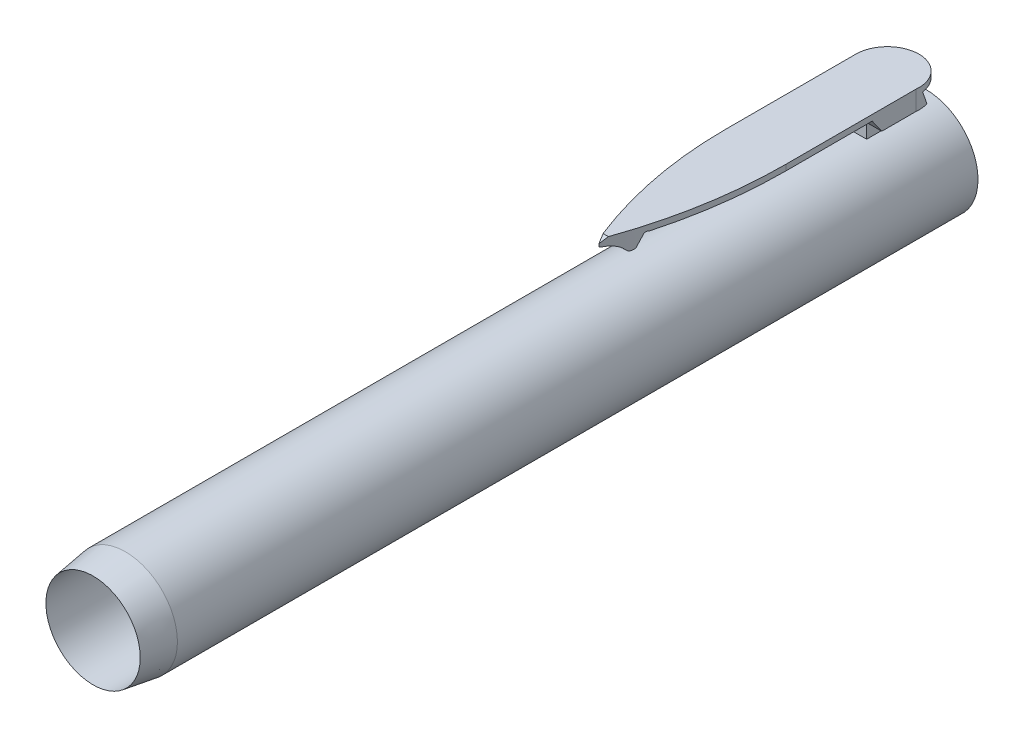
SolidWorks part; units mm, degrees
material "Cast Alloy Steel"
ref_plane "Front Plane" through (0, 0, 0) normal (0, 0, 1) x (1, 0, 0)
ref_plane "Top Plane" through (0, 0, 0) normal (0, 1, 0) x (1, 0, 0)
ref_plane "Right Plane" through (0, 0, 0) normal (1, 0, 0) x (0, 0, -1)
ref_axis "X-axis" through (-88.99, 0, 0) along (1, 0, 0)
ref_axis "Y-axis" through (0, 55, 0) along (0, -1, 0)
ref_axis "Z-axis" through (0, 0, -88.99) along (0, 0, 1)
sketch "Sketch2" plane through (0, 0, 0) normal (1, 0, 0) x (0, 0, -1)
  line L0 (0, 0) -> (60.3829, 0) construction
  line L1 (0, 6.1849) -> (106.7469, 6.1849)
  line L2 (0, 6.1849) -> (4.2394, 6.8199)
  line L3 (4.2394, 6.8199) -> (109.22, 6.8199)
  line L4 (109.22, 6.8199) -> (109.22, 6.1849)
  line L5 (106.7469, 6.1849) -> (106.7469, 3.81)
  line L6 (106.7469, 3.81) -> (109.22, 3.81)
  line L7 (109.22, 3.81) -> (109.22, 6.1849)
  dimension "D1" = 12.3698
  dimension "D2" = 109.22
  dimension "D3" = 0.635
  dimension "D4" = 7.62
revolve "Revolve1" add sketch "Sketch2" angle 360 about L0
ref_plane "Plane1" through (0, 6.8199, 0) normal (0, 1, 0) x (1, 0, 0)
sketch "Sketch3" plane through (0, 6.8199, 0) normal (0, 1, 0) x (1, 0, 0)
  line L1 (-1.761, 99.6768) -> (1.761, 99.6768)
  line L2 (-1.761, 99.6768) -> (-1.761, 105.7522)
  line L3 (-1.761, 105.7522) -> (1.761, 105.7522)
  line L4 (1.761, 99.6768) -> (1.761, 105.7522)
  line L5 (-1.761, 99.6768) -> (1.761, 105.7522) construction
  line L6 (-1.761, 105.7522) -> (1.761, 99.6768) construction
  point P0 (0, 102.7145)
extrude "Boss-Extrude1" add sketch "Sketch3" along normal blind 1.905 separate body
sketch "Sketch4" plane through (0, 8.7249, 0) normal (0, 1, 0) x (1, 0, 0)
  line L0 (-4.1727, 104.1606) -> (-4.1727, 87.1139)
  line L1 (3.7504, 104.1606) -> (3.7504, 87.1139)
  arc A0 (-4.1727, 87.1139) -> (0, 66.3457) centre (49.5963, 87.1139) ccw
  arc A1 (3.7504, 87.1139) -> (0, 66.3457) centre (-55.628, 87.1139) cw
  arc A2 (-4.1727, 104.1606) -> (0, 108.3333) centre (0, 104.1606) cw
  arc A3 (0, 108.3333) -> (3.7504, 104.1606) centre (0, 104.5616) cw
extrude "Boss-Extrude2" add sketch "Sketch4" along normal blind 2.54
sketch "Sketch5" plane through (3.7504, 0, 0) normal (1, 0, 0) x (0, 0, -1)
  line L16 (67.2439, 11.2649) -> (66.3457, 10.765)
  line L17 (87.1139, 11.2649) -> (66.3457, 11.2649) construction
  line L18 (66.3457, 11.2649) -> (66.3457, 8.7249) construction
  line L19 (66.3457, 10.765) -> (66.3457, 10.3454)
  line L20 (66.3457, 10.3454) -> (67.1, 10.2174)
  line L21 (69.9943, 9.1093) -> (70.7186, 10.3454)
  line L22 (71.3269, 10.5043) -> (98.4131, 10.5043)
  line L23 (98.4131, 10.5043) -> (99.6768, 8.7249)
  line L24 (99.6768, 8.7249) -> (66.3457, 8.7249)
  line L25 (66.3457, 8.7249) -> (66.3457, 10.3454)
  line L26 (67.2439, 11.2649) -> (66.3457, 11.2649)
  line L27 (66.3457, 11.2649) -> (66.3457, 10.765)
  line L28 (105.0284, 10.5123) -> (105.7522, 8.7249)
  line L29 (105.7522, 8.7249) -> (108.3333, 8.7249)
  line L30 (108.3333, 8.7249) -> (108.3333, 10.5123)
  line L31 (108.3333, 11.2649) -> (108.3333, 8.7249) construction
  line L32 (108.3333, 10.5123) -> (105.0284, 10.5123)
  arc A4 (67.1, 10.2174) -> (68.9593, 9.1778) centre (66.5679, 7.0832) cw
  arc A5 (68.9593, 9.1778) -> (69.9943, 9.1093) centre (69.5111, 9.6611) ccw
  arc A6 (70.7186, 10.3454) -> (71.3269, 10.5043) centre (71.1022, 10.1207) cw
  line M1 (87.1139, 8.7249) -> (104.1606, 8.7249)
  line M4 (87.1139, 11.2649) -> (87.1139, 8.7249)
extrude "Cut-Extrude2" cut sketch "Sketch5" against normal through all contours L30 L32 L28 L29 | L23 L22 M4 M1 | A6 L21 A5 A4 L20 L25 L24 L22 M4 | L26 L27 L16 region at (3.7504, 9.5795, -77.5396) region at (3.7504, 11.0983, -66.6451) region at (3.7504, 9.5989, -93.085) region at (3.7504, 9.6552, -106.8544)
